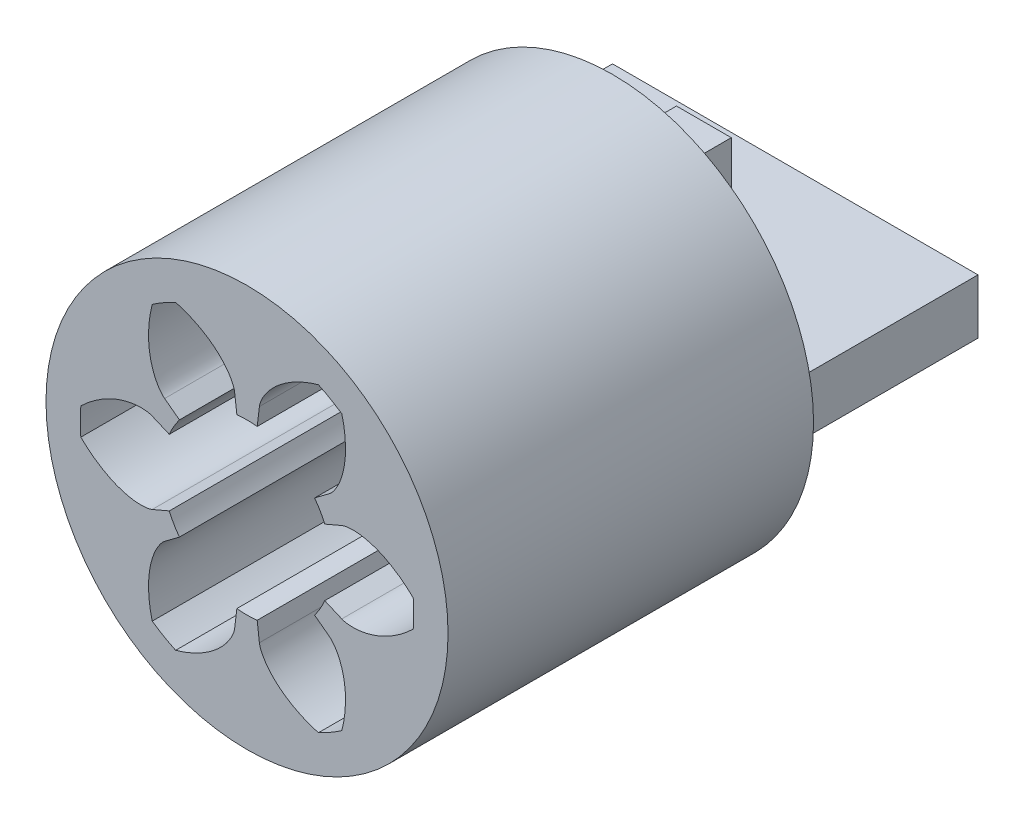
SolidWorks part; units mm, degrees
ref_plane "前视基准面" through (0, 0, 0) normal (0, 0, 1) x (1, 0, 0)
ref_plane "上视基准面" through (0, 0, 0) normal (0, 1, 0) x (1, 0, 0)
ref_plane "右视基准面" through (0, 0, 0) normal (1, 0, 0) x (0, 0, -1)
other "Configuration Table"
sketch "草图1" plane through (0, 0, 0) normal (0, 0, 1) x (1, 0, 0)
  line L0 (0, 0) -> (1.1087, 0.4592) construction
  line L1 (0, 0) -> (1.0372, 0.4425)
  line L2 (0, 0) -> (1.0372, -0.4425)
  line L3 (0, 0) -> (1.1087, -0.4592) construction
  line L4 (0, 0) -> (1.825, 0) construction
  line L5 (1.1087, 0.4592) -> (1.1087, -0.4592) construction
  circle A0 centre (0, 0) radius 0.925
  circle A1 centre (0, 0) radius 1.825
  circle A2 centre (0, 0) radius 1.1276 construction
  circle A3 centre (0, 0) radius 1.2 construction
  circle A4 centre (0, 0) radius 2.2
  spline S0 degree 4 poles (1.0372, 0.4425) (1.0451, 0.4458) (1.0679, 0.4536) (1.1133, 0.4615) (1.188, 0.4641) (1.2844, 0.4524) (1.4047, 0.4201) (1.5384, 0.3613) (1.6746, 0.2764) (1.8072, 0.1656) (1.9251, 0.0393) (2.0279, -0.0995) (2.12, -0.2556) (2.2132, -0.4598) (2.2925, -0.7157) (2.34, -1.0237) (2.3398, -1.3696) (2.2891, -1.712) (2.1939, -2.0438) (2.0552, -2.3616) (1.8823, -2.6586) (1.6708, -2.936) (1.4388, -3.184) (1.166, -3.413) (0.9461, -3.5671) (0.6842, -3.7168) (0.5292, -3.7919) (0.3505, -3.8722) (0.2497, -3.9065) (0.1672, -3.9381) (0.1423, -3.9451) (0.1243, -3.9513) knots 0 0 0 0 0 0.005604 0.015718 0.02996 0.048734 0.068727 0.096889 0.125051 0.153212 0.181374 0.209535 0.237696 0.271429 0.327752 0.384075 0.440398 0.496721 0.553044 0.609367 0.66569 0.722013 0.778336 0.834659 0.890982 0.909091 0.954545 0.977273 0.988636 1 1 1 1 1 construction
  spline S1 degree 4 poles (1.0372, 0.4425) (1.0451, 0.4458) (1.0679, 0.4536) (1.1133, 0.4615) (1.188, 0.4641) (1.2844, 0.4524) (1.4047, 0.4201) (1.5384, 0.3613) (1.6746, 0.2764) (1.8072, 0.1656) (1.9251, 0.0393) (2.0279, -0.0995) (2.12, -0.2556) (2.2132, -0.4598) (2.2925, -0.7157) (2.34, -1.0237) (2.3398, -1.3696) (2.2891, -1.712) (2.1939, -2.0438) (2.0552, -2.3616) (1.8823, -2.6586) (1.6708, -2.936) (1.4388, -3.184) (1.166, -3.413) (0.9461, -3.5671) (0.7517, -3.6782) (0.6596, -3.7265) (0.6372, -3.738) knots 0 0 0 0 0 0.005604 0.015718 0.02996 0.048734 0.068727 0.096889 0.125051 0.153212 0.181374 0.209535 0.237696 0.271429 0.327752 0.384075 0.440398 0.496721 0.553044 0.609367 0.66569 0.722013 0.778336 0.834659 0.890982 0.909091 0.909091 0.909091 0.909091 0.909091
  spline S2 degree 4 poles (1.0372, -0.4425) (1.0451, -0.4458) (1.0679, -0.4536) (1.1133, -0.4615) (1.188, -0.4641) (1.2844, -0.4524) (1.4047, -0.4201) (1.5384, -0.3613) (1.6746, -0.2764) (1.8072, -0.1656) (1.9251, -0.0393) (2.0279, 0.0995) (2.12, 0.2556) (2.2132, 0.4598) (2.2925, 0.7157) (2.34, 1.0237) (2.3398, 1.3696) (2.2891, 1.712) (2.1939, 2.0438) (2.0552, 2.3616) (1.8823, 2.6586) (1.6708, 2.936) (1.4388, 3.184) (1.166, 3.413) (0.9461, 3.5671) (0.6842, 3.7168) (0.5292, 3.7919) (0.3505, 3.8722) (0.2497, 3.9065) (0.1672, 3.9381) (0.1423, 3.9451) (0.1243, 3.9513) knots 0 0 0 0 0 0.005604 0.015718 0.02996 0.048734 0.068727 0.096889 0.125051 0.153212 0.181374 0.209535 0.237696 0.271429 0.327752 0.384075 0.440398 0.496721 0.553044 0.609367 0.66569 0.722013 0.778336 0.834659 0.890982 0.909091 0.954545 0.977273 0.988636 1 1 1 1 1 construction
  spline S3 degree 4 poles (1.0372, -0.4425) (1.0451, -0.4458) (1.0679, -0.4536) (1.1133, -0.4615) (1.188, -0.4641) (1.2844, -0.4524) (1.4047, -0.4201) (1.5384, -0.3613) (1.6746, -0.2764) (1.8072, -0.1656) (1.9251, -0.0393) (2.0279, 0.0995) (2.12, 0.2556) (2.2132, 0.4598) (2.2925, 0.7157) (2.34, 1.0237) (2.3398, 1.3696) (2.2891, 1.712) (2.1939, 2.0438) (2.0552, 2.3616) (1.8823, 2.6586) (1.6708, 2.936) (1.4388, 3.184) (1.166, 3.413) (0.9461, 3.5671) (0.7517, 3.6782) (0.6596, 3.7265) (0.6372, 3.738) knots 0 0 0 0 0 0.005604 0.015718 0.02996 0.048734 0.068727 0.096889 0.125051 0.153212 0.181374 0.209535 0.237696 0.271429 0.327752 0.384075 0.440398 0.496721 0.553044 0.609367 0.66569 0.722013 0.778336 0.834659 0.890982 0.909091 0.909091 0.909091 0.909091 0.909091
  point P16 (1.1087, 0)
  dimension "内啮合齿顶圆直径" = 1.85
  dimension "内啮合分度圆直径" = 2.4
  dimension "内啮合基圆直径" = 2.2553
  dimension "内啮合齿根圆直径" = 3.65
  dimension "外径" = 4.4
  dimension "渐开线镜像线夹角" = 22.5
extrude "凸台-拉伸1" add sketch "草图1" along normal blind 3 contours A4 | A0
extrude "切除-拉伸2" cut sketch "草图1<3>" along normal through all contours A0 S3 A1 S1 region at (1.3095, 0, 0)
sketch "草图1<3>" plane through (0, 0, 0) normal (0, 0, 1) x (1, 0, 0) same geometry as "草图1"
pattern_circular "阵列(圆周)1" count 6 over 360 about axis through (0, 0, 3) along (0, 0, 1) of "切除-拉伸2"
sketch "草图2" plane through (0, 0, 0) normal (0, 0, -1) x (-1, 0, 0)
  line L1 (-2, -0.3) -> (2, -0.3)
  line L2 (-2, -0.3) -> (-2, 0.3)
  line L3 (-2, 0.3) -> (2, 0.3)
  line L4 (2, -0.3) -> (2, 0.3)
  line L5 (-2, -0.3) -> (2, 0.3) construction
  line L6 (-2, 0.3) -> (2, -0.3) construction
  line L7 (0.3, -1.25) -> (-0.3, -1.25)
  line L8 (0.3, -1.25) -> (0.3, 1.25)
  line L9 (0.3, 1.25) -> (-0.3, 1.25)
  line L10 (-0.3, -1.25) -> (-0.3, 1.25)
  line L11 (0.3, -1.25) -> (-0.3, 1.25) construction
  line L12 (0.3, 1.25) -> (-0.3, -1.25) construction
  circle A0 centre (0, 0) radius 2.2
  circle A1 centre (0, 0) radius 2.2 construction
  dimension "D1" = 0.6
  dimension "D2" = 4
  dimension "D3" = 2.5
extrude "凸台-拉伸2" add sketch "草图2" along normal blind 1 contours A0
extrude "凸台-拉伸3" add sketch "草图2<3>" along normal blind 2 from surface contours L3 L4 L1 L2 starting at face at (-2.2, 0, -1)
sketch "草图2<3>" plane through (0, 0, 0) normal (0, 0, -1) x (-1, 0, 0) same geometry as "草图2"
extrude "凸台-拉伸4" add sketch "草图2<4>" along normal blind 1 from surface contours L10 L9 L8 L7 starting at face at (-2.2, 0, -1)
sketch "草图2<4>" plane through (0, 0, 0) normal (0, 0, -1) x (-1, 0, 0) same geometry as "草图2"
equation "\"m\"= 0.4'模数"
equation "\"z1\"= 6'外啮合齿轮数"
equation "\"a\"= 20度'压力角"
equation "\"z2\"= 6'内啮合齿轮数"
equation "\"hax\"= 1'齿顶高系数"
equation "\"cx\"= 0.25'顶隙系数"
equation "\"ha\"= \"hax\" * \"m\"'齿顶高"
equation "\"hf\"= ( \"hax\" + \"cx\" ) * \"m\"'齿根高"
equation "\"d1\"= \"m\" * \"z1\"'外啮合分度圆直径"
equation "\"da1\"= ( \"z1\" + 2 ) * \"m\"'外啮合齿顶圆直径"
equation "\"df1\"= \"d1\" - 2 * \"hf\"'外啮合齿根圆直径"
equation "\"db1\"= \"d1\" * cos ( \"a\" )'外啮合基圆直径"
equation "\"p\"= \"m\" * PI'齿距"
equation "\"d2\"= \"m\" * \"z2\"'内啮合分度圆直径"
equation "\"db2\"= \"d2\" * cos ( \"a\" )'内啮合基圆直径"
equation "\"da2\"= ( \"z2\" - 2 ) * \"m\"'内啮合齿顶圆直径"
equation "\"df2\"= \"d2\" + 2 * \"hf\"'内啮合齿根圆直径"
equation "\"内啮合齿顶圆直径@草图1\" = \"da2\" + 0.5 * \"hf\""
equation "\"内啮合齿根圆直径@草图1\"= \"df2\" + 0.5 * \"hf\""
equation "\"内啮合分度圆直径@草图1\"= \"d2\""
equation "\"内啮合基圆直径@草图1\"= \"db2\""
equation "\"渐开线镜像线夹角@草图1\"= 360度 / 4 / \"z2\" + 360度 / 4 / \"z2\" / 2"
equation "\"do\"= IIF ( \"edo\" >= ( \"df2\" + 1 ) , \"edo\" , ( \"df2\" + 1 ) )'外圈直径"
equation "\"h\"= 3'厚度"
equation "\"外径@草图1\"= \"do\""
equation "\"厚度@凸台-拉伸1\"= \"h\""
equation "\"内啮合齿轮数@阵列(圆周)1\"= \"z2\""
equation "\"edo\"= 3'期望的外圈直径"
